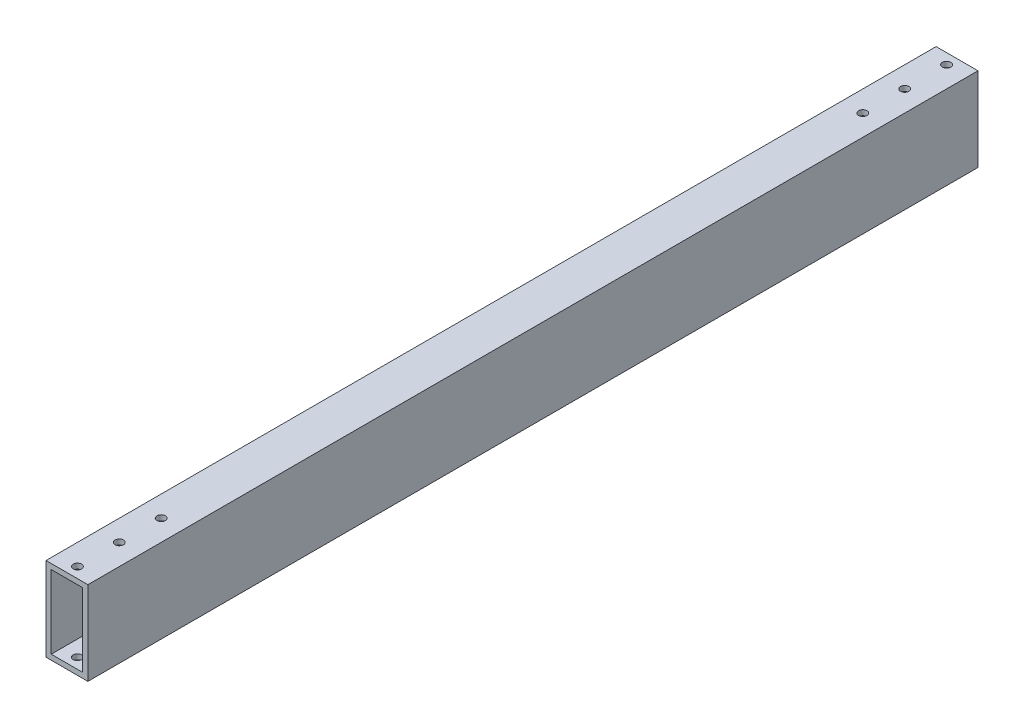
SolidWorks part; units mm, degrees
ref_plane "Front" through (0, 0, 0) normal (0, 0, 1) x (1, 0, 0)
ref_plane "Top" through (0, 0, 0) normal (0, 1, 0) x (1, 0, 0)
ref_plane "Right" through (0, 0, 0) normal (1, 0, 0) x (0, 0, -1)
sketch "Sketch1" plane through (0, 0, 0) normal (0, 0, 1) x (1, 0, 0)
  line L1 (-12.7, -25.4) -> (12.7, -25.4)
  line L2 (-12.7, -25.4) -> (-12.7, 25.4)
  line L3 (-12.7, 25.4) -> (12.7, 25.4)
  line L4 (12.7, -25.4) -> (12.7, 25.4)
  line L5 (-12.7, -25.4) -> (12.7, 25.4) construction
  line L6 (-12.7, 25.4) -> (12.7, -25.4) construction
  point P0 (0, 0)
  dimension "D1" = 25.4
  dimension "D2" = 50.8
extrude "Extrude-Thin1" add sketch "Sketch1" along normal blind 539.75 thin thin type one direction reverse wall 3.175
hole_wizard "#10 Clearance Hole1" positions "Sketch2" profile "Sketch3" hole size "#10" standard "ANSI Inch" end condition through all
sketch "Sketch2" plane through (0, 25.4, 0) normal (0, 1, 0) x (1, 0, 0)
  line L0 (12.7, -539.75) -> (-12.7, -539.75) construction
  line L1 (-12.7, -539.75) -> (-12.7, 0) construction
  point P0 (0, -533.4)
  point P2 (0, -508)
  point P4 (0, -482.6)
  point P13 (0, -6.35)
  point P15 (0, -31.75)
  point P17 (0, -57.15)
  point P19 (0, 0)
  point P21 (0, 0)
  point P22 (0, 0)
  point P23 (0, 0)
  point P24 (0, -8.9984)
  point P25 (0, 0)
  dimension "D1" = 6.35
  dimension "D2" = 25.4
  dimension "D3" = 25.4
  dimension "D4" = 12.7
  dimension "D5" = 6.35
  dimension "D6" = 25.4
  dimension "D7" = 25.4
sketch "Sketch3" plane through (0, 25.4, 533.4) normal (1, 0, 0) x (0, 0, 1)
  line L0 (0, 0) -> (0, 50.8)
  line L1 (0, 50.8) -> (2.5527, 50.8)
  line L2 (2.5527, 50.8) -> (2.5527, 0)
  line L5 (2.5527, 0) -> (0, 0)
  line L11 (0, -6.35) -> (0, 107.95) construction
  dimension "Thru Hole Dia." = 5.1054
  dimension "Thru Hole Depth" = 50.8
